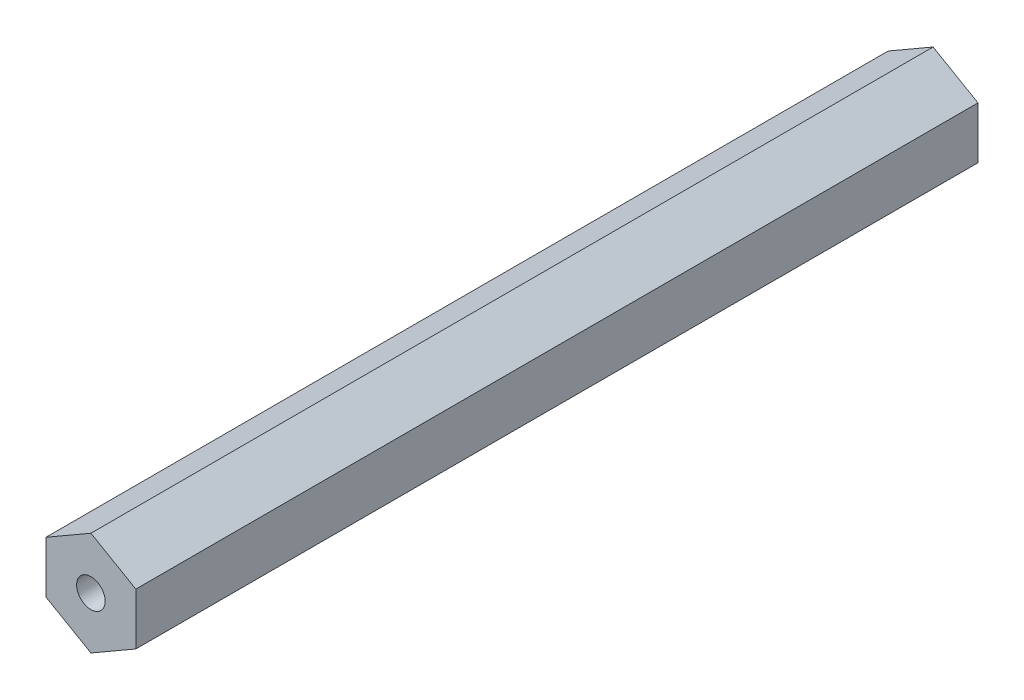
SolidWorks part; units mm, degrees
material "6061-T6 (SS)"
ref_plane "Front Plane" through (0, 0, 0) normal (0, 0, 1) x (1, 0, 0)
ref_plane "Top Plane" through (0, 0, 0) normal (0, 1, 0) x (1, 0, 0)
ref_plane "Right Plane" through (0, 0, 0) normal (1, 0, 0) x (0, 0, -1)
sketch "Sketch1" plane through (0, 0, 0) normal (0, 0, 1) x (1, 0, 0)
  line L7 (0, 7.3323) -> (-6.35, 3.6662)
  line L8 (-6.35, 3.6662) -> (-6.35, -3.6662)
  line L9 (-6.35, -3.6662) -> (0, -7.3323)
  line L10 (0, -7.3323) -> (6.35, -3.6662)
  line L11 (6.35, -3.6662) -> (6.35, 3.6662)
  line L12 (6.35, 3.6662) -> (0, 7.3323)
  circle A0 centre (0, 0) radius 6.35 construction
  point P1 (0, 0)
  point P7 (0, 0)
  dimension "D1" = 12.7
extrude "Boss-Extrude1" add sketch "Sketch1" along normal blind 119.0625 contours L7 L8 L9 L10 L11 L12
sketch "Sketch8" plane through (0, 0, 0) normal (0, 0, -1) x (-1, 0, 0)
  point P0 (0, 0)
hole_wizard "1/4-20 Tapped Hole2" positions "Sketch11" profile "Sketch12" tap size "1/4-20" standard "ANSI Inch"
sketch "Sketch11" plane through (0, 0, 0) normal (0, 0, -1) x (-1, 0, 0)
  point P0 (0, 0)
cosmetic thread "Hole Thread5" parameters "D1"=12.7, "D2"=6.35
sketch "Sketch12" plane through (0, 0, 0) normal (1, 0, 0) x (0, 1, 0)
  line L0 (0, 0) -> (0, 18.0438)
  line L1 (0, 18.0438) -> (2.5527, 16.51)
  line L2 (2.5527, 16.51) -> (2.5527, 0)
  line L5 (2.5527, 0) -> (0, 0)
  line L10 (0, 18.0438) -> (-2.5527, 16.51) construction
  line L11 (0, -6.35) -> (0, 107.95) construction
  dimension "Tap Drill Dia." = 5.1054
  dimension "Tap Drill Depth" = 16.51
  dimension "Drill Angle" = 118
sketch "Sketch14" plane through (0, 0, 119.0625) normal (0, 0, 1) x (1, 0, 0)
  line L7 (6.35, 3.6662) -> (0, 7.3323)
  line L8 (0, 7.3323) -> (-6.35, 3.6662)
  line L9 (6.35, 3.6662) -> (0, 7.3323)
  line L10 (-6.35, 3.6662) -> (-6.35, -3.6662)
  line L11 (-6.35, 3.6662) -> (-6.35, -3.6662)
  line L12 (-6.35, -3.6662) -> (0, -7.3323)
  line L14 (0, 7.3323) -> (-6.35, 3.6662)
  line L19 (-6.35, -3.6662) -> (0, -7.3323)
  line L20 (0, -7.3323) -> (6.35, -3.6662)
  line L21 (0, -7.3323) -> (6.35, -3.6662)
  line L22 (6.35, -3.6662) -> (6.35, 3.6662)
  line L23 (6.35, -3.6662) -> (6.35, 3.6662)
  dimension "D1" = 0
hole_wizard "#10-32 Tapped Hole1" positions "Sketch15" profile "Sketch16" tap size "#10-32" standard "ANSI Inch"
sketch "Sketch15" plane through (0, 0, 119.0625) normal (0, 0, 1) x (1, 0, 0)
  point P0 (0, 0)
sketch "Sketch16" plane through (0, 0, 119.0625) normal (1, 0, 0) x (0, -1, 0)
  line L0 (0, 0) -> (0, 14.8277)
  line L1 (0, 14.8277) -> (2.0193, 13.6144)
  line L2 (2.0193, 13.6144) -> (2.0193, 0)
  line L5 (2.0193, 0) -> (0, 0)
  line L10 (0, 14.8277) -> (-2.0193, 13.6144) construction
  line L11 (0, -6.35) -> (0, 107.95) construction
  dimension "Tap Drill Dia." = 4.0386
  dimension "Tap Drill Depth" = 13.6144
  dimension "Drill Angle" = 118
cosmetic thread "Hole Thread6" parameters "D1"=9.652, "D2"=4.826
